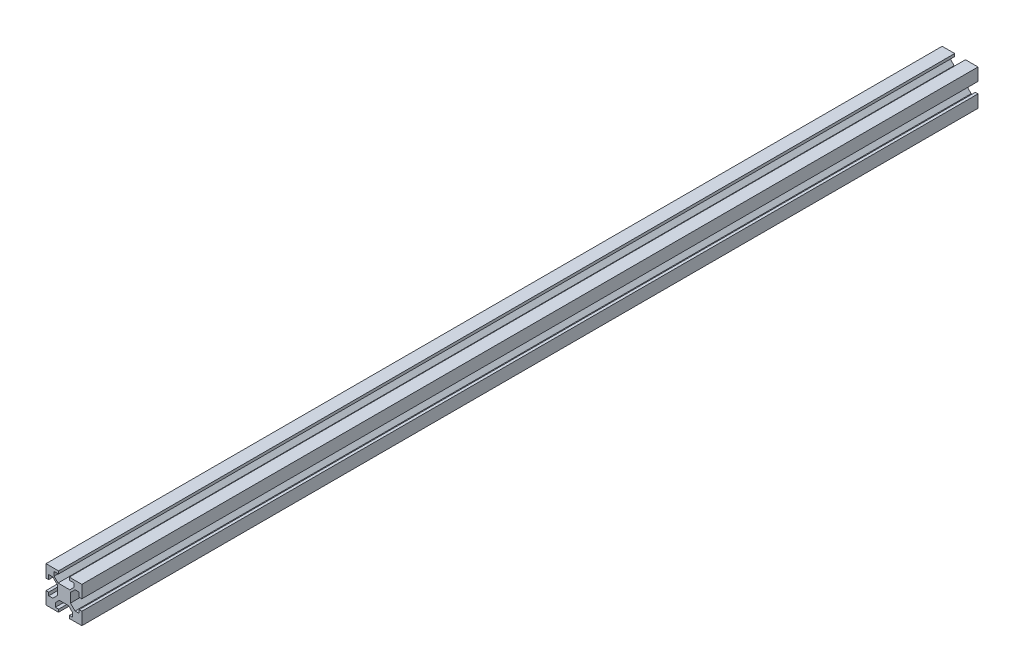
SolidWorks part; units mm, degrees
ref_plane "Front Plane" through (0, 0, 0) normal (0, 0, 1) x (1, 0, 0)
ref_plane "Top Plane" through (0, 0, 0) normal (0, 1, 0) x (1, 0, 0)
ref_plane "Right Plane" through (0, 0, 0) normal (1, 0, 0) x (0, 0, -1)
sketch "Sketch1" plane through (0, 0, 0) normal (0, 0, 1) x (1, 0, 0)
  line L0 (-10, 3) -> (-10, 10)
  line L1 (10, -10) -> (-10, -10) construction
  line L2 (10, -10) -> (10, 10) construction
  line L3 (10, 10) -> (-10, 10) construction
  line L4 (-10, -10) -> (-10, 10) construction
  line L5 (10, -10) -> (-10, 10) construction
  line L6 (10, 10) -> (-10, -10) construction
  line L7 (-10, 10) -> (-3, 10)
  line L8 (-3, 10) -> (-3, 8.5)
  line L9 (-3, 8.5) -> (-5.5, 8.5)
  line L10 (-5.5, 8.5) -> (-5.5, 6.2071)
  line L11 (-5.5, 6.2071) -> (-3.2929, 4)
  line L12 (0, 14.0643) -> (0, -17.0468) construction
  line L13 (-3.2929, 4) -> (3.2929, 4)
  line L14 (-10, 3) -> (-8.5, 3)
  line L15 (-8.5, 3) -> (-8.5, 5.5)
  line L16 (-8.5, 5.5) -> (-6.2071, 5.5)
  line L17 (-6.2071, 5.5) -> (-3.6457, 2.9386)
  line L18 (-3.6457, 2.9386) -> (-3.6457, -2.2314)
  line L19 (-10, -10) -> (-10, -3)
  line L20 (-10, -3) -> (-8.5, -3)
  line L21 (-8.5, -3) -> (-8.5, -4.7929)
  line L22 (-8.5, -4.7929) -> (-6.2071, -4.7929)
  line L23 (-6.2071, -4.7929) -> (-3.6457, -2.2314)
  line L24 (-10, -10) -> (-3, -10)
  line L25 (-3, -10) -> (-3, -8.5)
  line L26 (-3, -8.5) -> (-4.7929, -8.5)
  line L27 (-4.7929, -8.5) -> (-4.7929, -6.2071)
  line L28 (13.2183, 0) -> (-13.2183, 0) construction
  line L29 (-4.7929, -6.2071) -> (-2.5858, -4)
  line L30 (-2.5858, -4) -> (2.5858, -4)
  line L31 (4.7929, -6.2071) -> (2.5858, -4)
  line L32 (4.7929, -8.5) -> (4.7929, -6.2071)
  line L33 (3, -8.5) -> (4.7929, -8.5)
  line L34 (3, -10) -> (3, -8.5)
  line L35 (10, -10) -> (3, -10)
  line L36 (6.2071, -4.7929) -> (3.6457, -2.2314)
  line L37 (8.5, -4.7929) -> (6.2071, -4.7929)
  line L38 (8.5, -3) -> (8.5, -4.7929)
  line L39 (10, -3) -> (8.5, -3)
  line L40 (10, -10) -> (10, -3)
  line L41 (3.6457, 2.9386) -> (3.6457, -2.2314)
  line L42 (6.2071, 5.5) -> (3.6457, 2.9386)
  line L43 (8.5, 5.5) -> (6.2071, 5.5)
  line L44 (8.5, 3) -> (8.5, 5.5)
  line L45 (10, 3) -> (8.5, 3)
  line L46 (5.5, 6.2071) -> (3.2929, 4)
  line L47 (5.5, 8.5) -> (5.5, 6.2071)
  line L48 (3, 8.5) -> (5.5, 8.5)
  line L49 (3, 10) -> (3, 8.5)
  line L50 (10, 10) -> (3, 10)
  line L51 (10, 3) -> (10, 10)
  point P0 (0, 0)
  point P30 (0, 0)
  point P33 (0, -4)
  point P49 (0, 4)
  dimension "D1" = 20
  dimension "D2" = 20
  dimension "D3" = 7
  dimension "D4" = 1
  dimension "D5" = 1.5
  dimension "D6" = 1
  dimension "D7" = 8
  dimension "D8" = 5.17
  dimension "D9" = 4.5
extrude "Boss-Extrude1" add sketch "Sketch1" against normal blind 500
